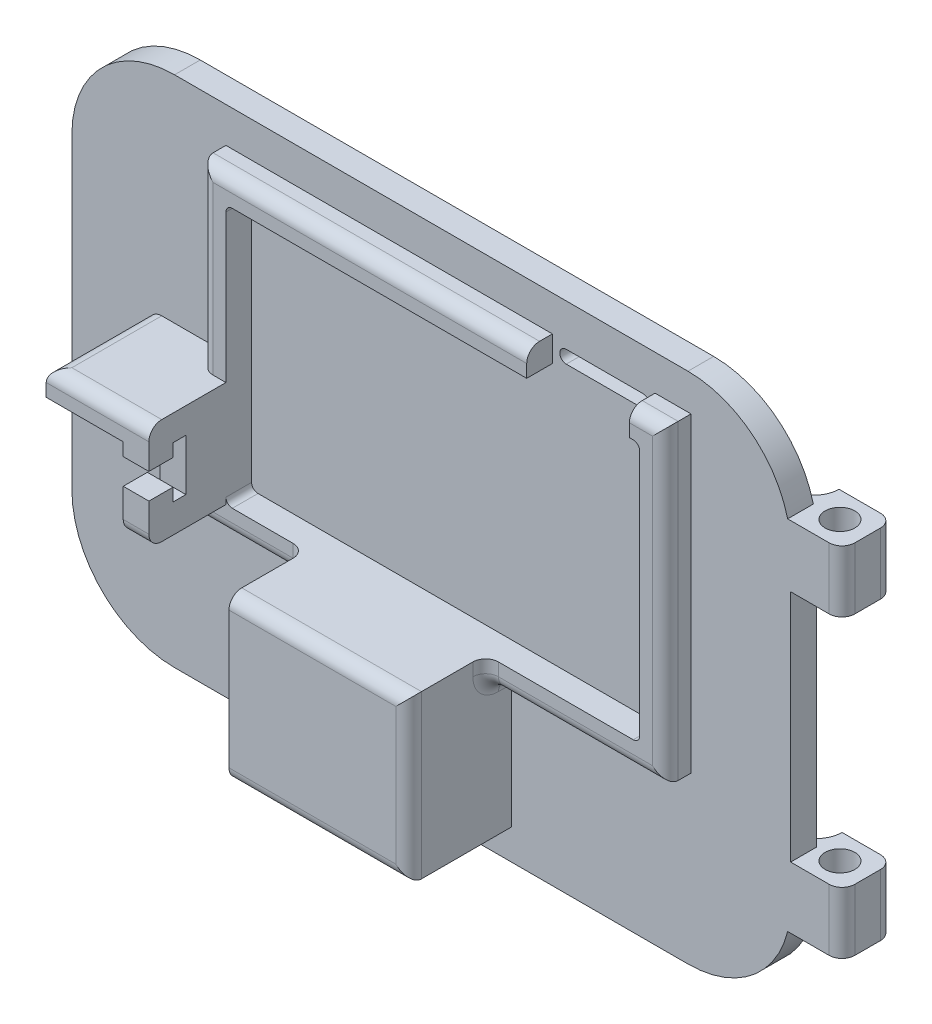
SolidWorks part; units mm, degrees
ref_plane "Front Plane" through (0, 0, 0) normal (0, 0, 1) x (1, 0, 0)
ref_plane "Top Plane" through (0, 0, 0) normal (0, 1, 0) x (1, 0, 0)
ref_plane "Right Plane" through (0, 0, 0) normal (1, 0, 0) x (0, 0, -1)
sketch "Sketch1" plane through (0, 0, 0) normal (0, 0, 1) x (1, 0, 0)
  line L0 (-63.5, 63.5) -> (63.5, 63.5)
  line L1 (63.5, -63.5) -> (-63.5, -63.5)
  line L2 (-88.9, -38.1) -> (-88.9, 38.1)
  line L3 (88.9, -38.1) -> (88.9, 38.1)
  arc A0 (-88.9, 38.1) -> (-63.5, 63.5) centre (-63.5, 38.1) cw
  arc A1 (-63.5, -63.5) -> (-88.9, -38.1) centre (-63.5, -38.1) cw
  arc A2 (63.5, -63.5) -> (88.9, -38.1) centre (63.5, -38.1) ccw
  arc A3 (88.9, 38.1) -> (63.5, 63.5) centre (63.5, 38.1) ccw
  dimension "D1" = 25.4
  dimension "D2" = 88.9
  dimension "D3" = 88.9
  dimension "D4" = 63.5
  dimension "D5" = 63.5
extrude "Boss-Extrude1" add sketch "Sketch1" against normal blind 6.35
sketch "Sketch3" plane through (0, 0, 0) normal (0, 0, 1) x (1, 0, 0)
  line L0 (63.5, 63.5) -> (88.9, 63.5) construction
  line L1 (88.9, 63.5) -> (101.6, 63.5) construction
  line L6 (101.6, 28.956) -> (101.6, 44.196)
  line L8 (101.6, 44.196) -> (88.1576, 44.196)
  line L9 (101.6, 63.5) -> (101.6, 28.956) construction
  line L10 (101.6, 28.956) -> (88.9, 28.956)
  line L11 (88.9, -38.1) -> (88.9, 38.1) construction
  line L12 (88.9, 28.956) -> (88.9, 38.1)
  arc A0 (88.9, 38.1) -> (88.1576, 44.196) centre (63.5, 38.1) ccw
  dimension "D5" = 25.4
  dimension "D1" = 25.4
  dimension "D2" = 12.7
  dimension "D3" = 34.544
  dimension "D4" = 19.304
extrude "Boss-Extrude2" add sketch "Sketch3" against normal blind 12.7
sketch "Sketch4" plane through (0, 44.196, 0) normal (0, 1, 0) x (1, 0, 0)
  line L0 (101.6, 6.35) -> (94.75, 6.35) construction
  line L1 (101.6, 12.7) -> (101.6, 0) construction
  circle A0 centre (94.75, 6.35) radius 3.675
  point P6 (98.425, 6.35)
  dimension "D1" = 7.35
  dimension "D2" = 3.175
extrude "Cut-Extrude2" cut sketch "Sketch4" against normal up to next
sketch "Sketch5" plane through (0, 0, 0) normal (0, 0, 1) x (1, 0, 0)
  line L0 (0, 0) -> (88.9402, 0)
mirror "Mirror1" about plane through (0, 0, 0) normal (0, 1, 0) of "Cut-Extrude2", "Boss-Extrude2"
sketch "Sketch7" plane through (0, 0, -6.35) normal (0, 0, -1) x (-1, 0, 0)
  line L0 (0, 0) -> (57.15, 0) construction
  point P4 (57.15, 0)
  dimension "D1" = 57.15
ref_plane "Plane1" through (-57.15, 0, -6.35) normal (-1, 0, 0) x (0, 0, 1)
sketch "Sketch8" plane through (-57.15, 0, -6.35) normal (-1, 0, 0) x (0, 0, 1)
  line L0 (0, 0) -> (0, 38.1) construction
  line L1 (0, 38.1) -> (0, 44.45)
  line L2 (-19.05, 25.4) -> (-19.05, -25.4)
  line L3 (0, 24.7494) -> (-24.0575, 24.7494) construction
  line L4 (-12.7, 25.4) -> (-12.7, 40.5526) construction
  line L5 (-19.05, 0) -> (-12.7, 0) construction
  line L6 (-12.7, -25.4) -> (-12.7, 25.4)
  line L7 (0, -38.1) -> (0, -44.45)
  arc A0 (0, 44.45) -> (-19.05, 25.4) centre (0, 25.4) ccw
  arc A1 (0, 38.1) -> (-12.7, 25.4) centre (0, 25.4) ccw
  arc A2 (0, -38.1) -> (-12.7, -25.4) centre (0, -25.4) cw
  arc A3 (0, -44.45) -> (-19.05, -25.4) centre (0, -25.4) cw
  dimension "D1" = 38.1
  dimension "D2" = 6.35
  dimension "D3" = 19.7006
  dimension "D4" = 12.7
extrude "Boss-Extrude3" add sketch "Sketch8" against normal blind 12.7
fillet "Fillet1" radius 6.35 1 edges at (-50.8, -44.45, -6.35)
fillet "Fillet2" radius 6.35 1 edges at (-57.15, -44.0467, -6.35)
fillet "Fillet3" radius 6.35 1 edges at (-44.45, -44.0467, -6.35)
fillet "Fillet4" radius 6.35 3 edges at (-50.8, 44.45, -6.35) (-44.45, 41.275, -6.35) (-57.15, 41.275, -6.35)
sketch "Sketch9" plane through (0, 0, 0) normal (0, 0, 1) x (1, 0, 0)
  line L0 (88.9402, 0) -> (-88.9, 0) construction
  line L1 (-88.9, 38.1) -> (-88.9, -38.1) construction
  line L22 (57.9, 48.375) -> (-44.45, 48.375)
  line L23 (57.9, 48.375) -> (57.9, -15.875)
  line L24 (57.9, -15.875) -> (-44.45, -15.875)
  line L25 (-44.45, 48.375) -> (-44.45, -15.875)
  line L26 (-63.5, -63.5) -> (63.5, -63.5) construction
  line L28 (64.25, 54.725) -> (64.25, -22.225)
  line L29 (64.25, -22.225) -> (-50.8, -22.225)
  line L30 (-50.8, 54.725) -> (-50.8, -22.225)
  line L31 (64.25, 54.725) -> (-50.8, 54.725)
  dimension "D1" = 64.25
  dimension "D2" = 102.35
  dimension "D3" = 47.625
  dimension "D4" = 38.1
  dimension "D5" = 6.35
extrude "Boss-Extrude4" add sketch "Sketch9" along normal blind 6.35
sketch "Sketch10" plane through (0, 0, 0) normal (0, 0, 1) x (1, 0, 0)
  line L0 (-44.45, 48.375) -> (-44.45, 10.9459) construction
  line L1 (57.9, -15.875) -> (57.9, 51.55) construction
  line L2 (33.389, 51.55) -> (52.439, 51.55) construction
  line L3 (33.389, 53.1375) -> (52.439, 53.1375)
  line L4 (33.389, 49.9625) -> (52.439, 49.9625)
  line L5 (57.9, 51.55) -> (42.914, 51.55) construction
  line L6 (64.25, 54.725) -> (64.25, 51.55) construction
  line L7 (64.25, -22.225) -> (64.25, 54.725) construction
  arc A0 (33.389, 53.1375) -> (33.389, 49.9625) centre (33.389, 51.55) ccw
  arc A1 (52.439, 49.9625) -> (52.439, 53.1375) centre (52.439, 51.55) ccw
  point P6 (42.914, 51.55)
  point P16 (0, 0)
  point P20 (0, 0)
  dimension "D1" = 3.175
  dimension "D2" = 14.986
  dimension "D3" = 19.05
  dimension "D4" = 3.175
extrude "Cut-Extrude3" cut sketch "Sketch10" against normal up to next and the other way up to next
sketch "Sketch14" plane through (0, 0, 0) normal (0, 0, 1) x (1, 0, 0)
  line L0 (13.45, -22.225) -> (13.45, -49.657)
  line L1 (-50.8, -22.225) -> (64.25, -22.225) construction
  line L2 (13.45, -49.657) -> (-24.65, -49.657)
  line L3 (64.25, -22.225) -> (64.25, 54.725) construction
  line L4 (19.8, -22.225) -> (19.8, -56.007)
  line L5 (19.8, -56.007) -> (-24.65, -56.007)
  line L6 (-24.65, -56.007) -> (-24.65, -49.657)
  line L7 (19.8, -15.875) -> (-24.65, -15.875)
  line L8 (-44.45, -15.875) -> (57.9, -15.875) construction
  line L9 (-24.65, -15.875) -> (-24.65, -22.225)
  line L10 (-24.65, -22.225) -> (13.45, -22.225)
  line L11 (19.8, -22.225) -> (19.8, -15.875)
  dimension "D1" = 38.1
  dimension "D2" = 27.432
  dimension "D3" = 50.8
  dimension "D4" = 6.35
extrude "Boss-Extrude7" add sketch "Sketch14" along normal blind 25.4
sketch "Sketch15" plane through (0, -49.657, 0) normal (0, 1, 0) x (1, 0, 0)
  line L0 (-24.65, -25.4) -> (-24.65, -19.05)
  line L1 (-24.65, -25.4) -> (-24.65, 0) construction
  line L2 (-24.65, -19.05) -> (13.45, -19.05)
  line L3 (13.45, -25.4) -> (13.45, 0) construction
  line L4 (13.45, -19.05) -> (13.45, -25.4)
  line L5 (13.45, -25.4) -> (-24.65, -25.4)
  dimension "D1" = 6.35
extrude "Boss-Extrude8" add sketch "Sketch15" along normal up to next
sketch "Sketch16" plane through (0, 0, 0) normal (0, 0, 1) x (1, 0, 0)
  line L0 (-50.8, 3.925) -> (-69.85, 3.925)
  line L1 (-50.8, 54.725) -> (-50.8, -22.225) construction
  line L2 (64.25, 54.725) -> (-50.8, 54.725) construction
  line L3 (-69.85, 10.275) -> (-69.85, 3.925)
  line L4 (-50.8, 10.275) -> (-44.45, 10.275)
  line L5 (-44.45, 48.375) -> (-44.45, -15.875) construction
  line L6 (-44.45, 10.275) -> (-44.45, -15.875)
  line L7 (-44.45, -15.875) -> (-50.8, -15.875)
  line L8 (-50.8, -15.875) -> (-50.8, 3.925)
  line L9 (-44.45, -15.875) -> (-24.65, -15.875) construction
  line L13 (-50.8, 10.275) -> (-69.85, 10.275)
  point P8 (-47.625, -15.875)
  dimension "D1" = 19.05
  dimension "D2" = 50.8
  dimension "D3" = 6.35
extrude "Boss-Extrude9" add sketch "Sketch16" along normal blind 25.4
sketch "Sketch17" plane through (-50.8, 0, 0) normal (-1, 0, 0) x (0, 0, 1)
  line L0 (0, 3.925) -> (16.256, 3.925) construction
  line L1 (0, 3.925) -> (25.4, 3.925) construction
  line L2 (16.256, 3.925) -> (16.256, -8.775)
  line L3 (16.256, -8.775) -> (19.431, -8.775)
  line L4 (19.431, -8.775) -> (19.431, 3.925)
  line L5 (19.431, 3.925) -> (16.256, 3.925)
  dimension "D1" = 16.256
  dimension "D2" = 12.7
  dimension "D3" = 3.175
extrude "Cut-Extrude4" cut sketch "Sketch17" against normal up to next
sketch "Sketch18" plane through (0, 0, 25.4) normal (0, 0, 1) x (1, 0, 0)
  line L0 (-50.8, 0.75) -> (-44.45, 0.75) construction
  line L1 (-44.45, -15.875) -> (-44.45, 10.275) construction
  line L4 (-50.8, 3.925) -> (-50.8, -15.875) construction
  line L5 (-44.45, 0.75) -> (-50.8, 0.75)
  line L6 (-44.45, 0.75) -> (-44.45, -5.6)
  line L7 (-44.45, -5.6) -> (-50.8, -5.6)
  line L8 (-50.8, 0.75) -> (-50.8, -5.6)
  line L9 (-44.45, 0.75) -> (-50.8, -5.6) construction
  line L10 (-44.45, -5.6) -> (-50.8, 0.75) construction
  line L11 (-44.45, 48.375) -> (-44.45, -15.875) construction
  line L12 (-69.85, 3.925) -> (-50.8, 3.925) construction
  dimension "D1" = 6.35
  dimension "D2" = 3.175
extrude "Cut-Extrude5" cut sketch "Sketch18" against normal up to next
fillet "Fillet6" radius 3.175 16 edges at (19.8, -35.941, 25.4) (-2.425, -15.875, 25.4) (-2.425, -56.007, 25.4) (-24.65, -22.225, 12.7) (19.8, -22.225, 3.175) (-50.8, 32.5, 6.35) (-50.8, -19.05, 6.35) (-37.725, -22.225, 6.35) (42.025, -22.225, 6.35) (64.25, 16.25, 6.35) (6.725, 54.725, 6.35) (-24.65, -19.05, 6.35) (19.8, -19.05, 6.35) (-69.85, 10.275, 12.7) (-57.15, 10.275, 25.4) (-47.625, -15.875, 25.4)
fillet "Fillet9" radius 6.35 4 edges at (88.9, -33.528, -6.35) (88.9, 33.528, -6.35) (88.7137, -41.1705, -6.35) (88.7137, 41.1705, -6.35)
fillet "Fillet10" radius 3.175 4 edges at (101.6, 36.576, -12.7) (101.6, 36.576, 0) (101.6, -36.576, 0) (101.6, -36.576, -12.7)
sketch "Sketch19" plane through (0, 0, 6.35) normal (0, 0, 1) x (1, 0, 0)
  line L0 (43.6125, -22.225) -> (43.6125, 51.55) construction
  line L1 (22.975, -22.225) -> (64.25, -22.225) construction
  line L2 (61.075, 51.55) -> (54.0265, 51.55) construction
  line L3 (55.36, 48.375) -> (55.36, 54.725)
  line L4 (64.25, 54.725) -> (-50.8, 54.725) construction
  line L5 (55.36, 54.725) -> (29.96, 54.725)
  line L6 (29.96, 54.725) -> (29.96, 48.375)
  line L7 (57.9, 48.375) -> (-44.45, 48.375) construction
  line L8 (29.96, 48.375) -> (55.36, 48.375)
  line L9 (57.9, -15.875) -> (57.9, 48.375) construction
  dimension "D1" = 25.4
  dimension "D2" = 2.54
extrude "Cut-Extrude6" cut sketch "Sketch19" against normal up to surface (6.35 mm away) up to face at (6.725, 16.25, 0)
fillet "Fillet11" radius 1.5875 4 edges at (57.9, 48.375, 3.175) (-44.45, 48.375, 3.175) (-44.45, -15.875, 3.175) (57.9, -15.875, 3.175)
